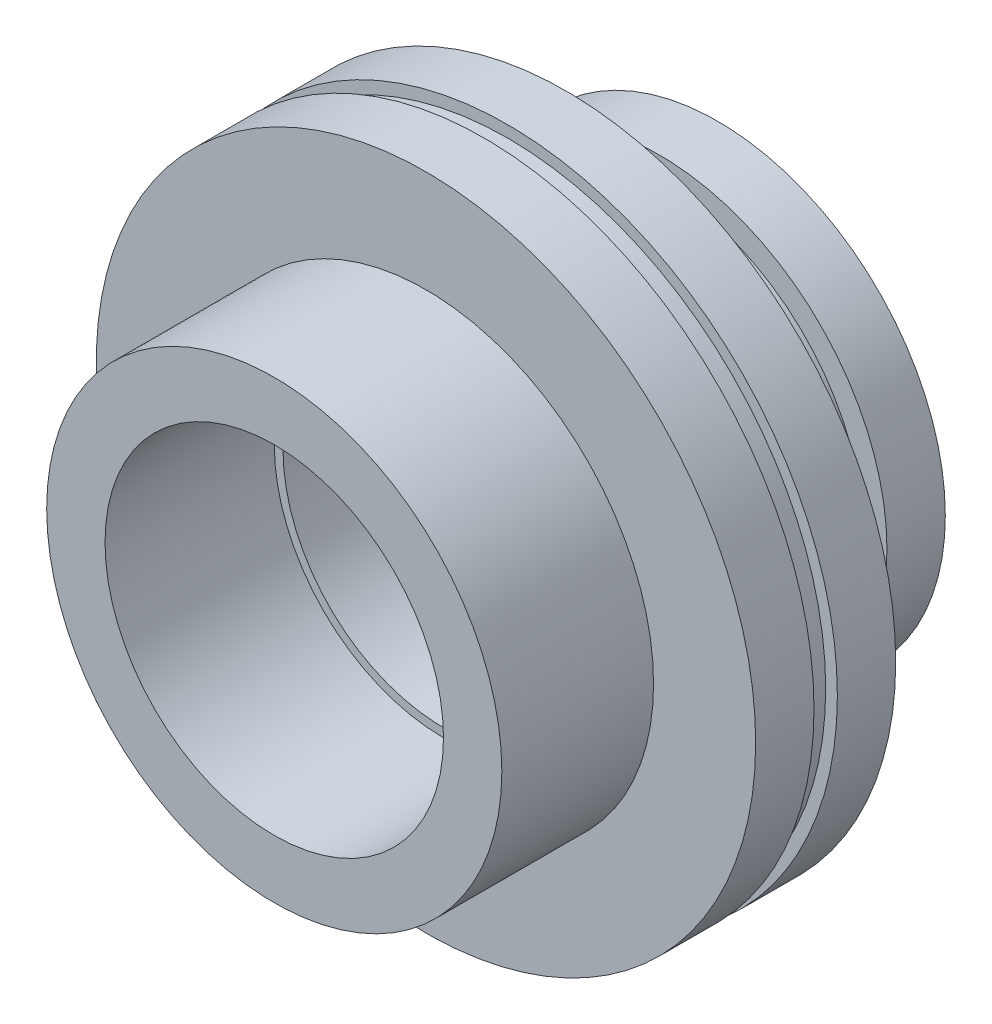
SolidWorks part; units mm, degrees
ref_plane "前视基准面" through (0, 0, 0) normal (0, 0, 1) x (1, 0, 0)
ref_plane "上视基准面" through (0, 0, 0) normal (0, 1, 0) x (1, 0, 0)
ref_plane "右视基准面" through (0, 0, 0) normal (1, 0, 0) x (0, 0, -1)
sketch "草图1" plane through (0, 0, 0) normal (0, 0, 1) x (1, 0, 0)
  circle A0 centre (0, 0) radius 56.5
  dimension "D1" = 113
extrude "凸台-拉伸1" add sketch "草图1" along normal blind 12 and the other way blind 12
sketch "草图2" plane through (0, 0, 0) normal (0, 0, 1) x (1, 0, 0)
  circle A0 centre (0, 0) radius 54.5
  circle A1 centre (0, 0) radius 74.8996
  dimension "D1" = 109
extrude "切除-拉伸1" cut sketch "草图2" against normal blind 2 and the other way blind 2
sketch "草图3" plane through (0, 0, -12) normal (0, 0, -1) x (-1, 0, 0)
  circle A0 centre (0, 0) radius 39
  dimension "D1" = 78
extrude "凸台-拉伸2" add sketch "草图3" along normal blind 26
mirror "镜向1" about plane through (0, 0, 0) normal (0, 0, 1) of "凸台-拉伸2"
ref_plane "基准面1" through (0, 0, -25) normal (0, 0, -1) x (-1, 0, 0)
sketch "草图4" plane through (0, 0, -25) normal (0, 0, -1) x (-1, 0, 0)
  circle A0 centre (0, 0) radius 35
  circle A1 centre (0, 0) radius 52.4834
  dimension "D1" = 70
extrude "切除-拉伸2" cut sketch "草图4" against normal blind 3 and the other way blind 3
sketch "草图5" plane through (0, 0, 38) normal (0, 0, 1) x (1, 0, 0)
  circle A0 centre (0, 0) radius 27.5
  dimension "D1" = 55
extrude "切除-拉伸3" cut sketch "草图5" against normal blind 80
ref_plane "基准面2" through (0, 0, 9) normal (0, 0, 1) x (1, 0, 0)
sketch "草图6" plane through (0, 0, 9) normal (0, 0, 1) x (1, 0, 0)
  circle A0 centre (0, 0) radius 29
  dimension "D1" = 58
extrude "切除-拉伸4" cut sketch "草图6" along normal blind 50
mirror "镜向2" about plane through (0, 0, 0) normal (0, 0, 1) of "切除-拉伸4"
